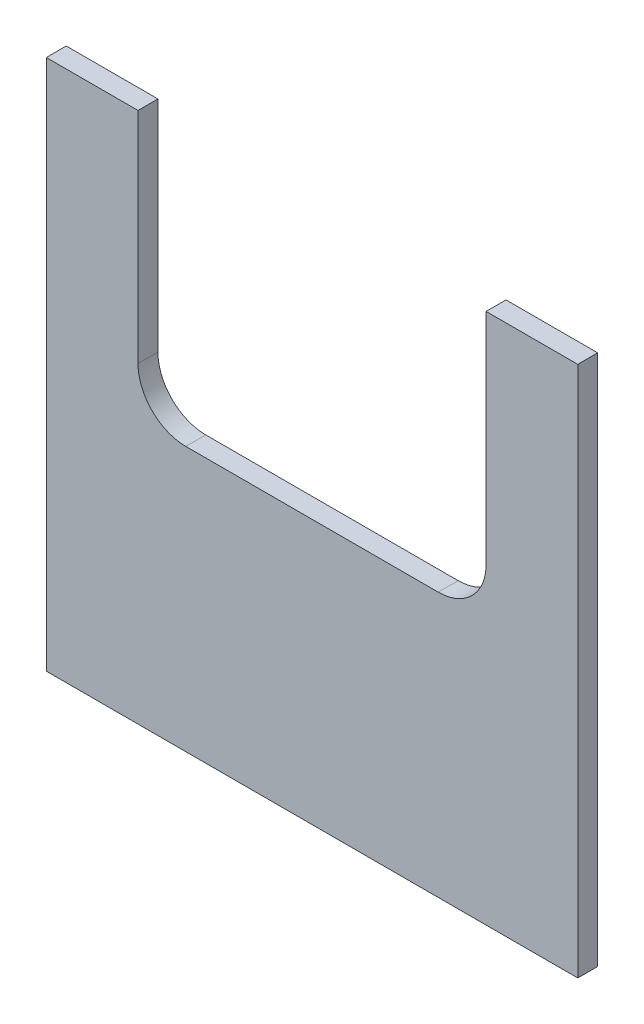
SolidWorks part; units mm, degrees
ref_plane "Ön Düzlem" through (0, 0, 0) normal (0, 0, 1) x (1, 0, 0)
ref_plane "Üst Düzlem" through (0, 0, 0) normal (0, 1, 0) x (1, 0, 0)
ref_plane "Sağ Düzlem" through (0, 0, 0) normal (1, 0, 0) x (0, 0, -1)
sketch "Çizim1" plane through (0, 0, 0) normal (0, 0, 1) x (1, 0, 0)
  line L0 (-164.9103, -3.6551) -> (-164.9103, 161.3449) construction
  line L1 (-129.9103, -38.6551) -> (60.0897, -38.6551) construction
  line L2 (95.0897, 161.3449) -> (95.0897, -3.6551) construction
  line L3 (-164.9103, 161.3449) -> (-234.9103, 161.3449) construction
  line L4 (-234.9103, 161.3449) -> (-234.9103, -238.6551)
  line L5 (-234.9103, -238.6551) -> (165.0897, -238.6551)
  line L6 (165.0897, -238.6551) -> (165.0897, 161.3449)
  line L7 (165.0897, 161.3449) -> (95.0897, 161.3449) construction
  line L8 (-34.9103, -38.6551) -> (-34.9103, -238.6551) construction
  line L9 (96.0897, 161.3449) -> (96.0897, -3.6551)
  line L10 (-129.9103, -39.6551) -> (60.0897, -39.6551)
  line L11 (-165.9103, -3.6551) -> (-165.9103, 161.3449)
  line L12 (96.0897, 161.3449) -> (165.0897, 161.3449)
  line L13 (-234.9103, 161.3449) -> (-165.9103, 161.3449)
  arc A0 (-164.9103, -3.6551) -> (-129.9103, -38.6551) centre (-129.9103, -3.6551) ccw construction
  arc A1 (60.0897, -38.6551) -> (95.0897, -3.6551) centre (60.0897, -3.6551) ccw construction
  arc A2 (60.0897, -39.6551) -> (96.0897, -3.6551) centre (60.0897, -3.6551) ccw
  arc A3 (-165.9103, -3.6551) -> (-129.9103, -39.6551) centre (-129.9103, -3.6551) ccw
  dimension "D7" = 36
  dimension "D8" = 36
  dimension "D14" = 1
  dimension "D16" = 35
  dimension "D17" = 1
  dimension "D1" = 400
  dimension "D2" = 400
  dimension "D3" = 69
  dimension "D4" = 262
  dimension "D5" = 201
  dimension "D6" = 69
  dimension "D9" = 165
  dimension "D10" = 190
  dimension "D11" = 400
  dimension "D12" = 165
  dimension "D13" = 1
  dimension "D15" = 1
  dimension "D18" = 190
  dimension "D19" = 35
  dimension "D20" = 35
base flange "Taban-Flanş1" sketch "Çizim1" thickness 15 reverse thickness direction no parameters "D1"=25
sketch "Büküm-Çizgileri1" [suppressed] plane through (0, 0, 0) normal (0, 1, 0) x (1, 0, 0)
sketch "Sınırlandırma-Kutusu1" [suppressed] plane through (0, 0, 0) normal (0, 1, 0) x (1, 0, 0)
sheet metal parameters "Sac-Levha1" thickness 15 parameters "D1"=25
flat pattern "Düz-Çoğaltma1" [suppressed]
sketch "Büküm-Çizgileri2" plane through (0, 0, 0) normal (0, 1, 0) x (1, 0, 0)
sketch3d "Sınırlandırma-Kutusu2" [suppressed]
  line L0 (-105, -235, 0) -> (295, -235, 0) construction
  line L1 (-105, 165, 0) -> (295, 165, 0) construction
  line L2 (-105, -235, 0) -> (-105, 165, 0) construction
  line L3 (295, -235, 0) -> (295, 165, 0) construction
